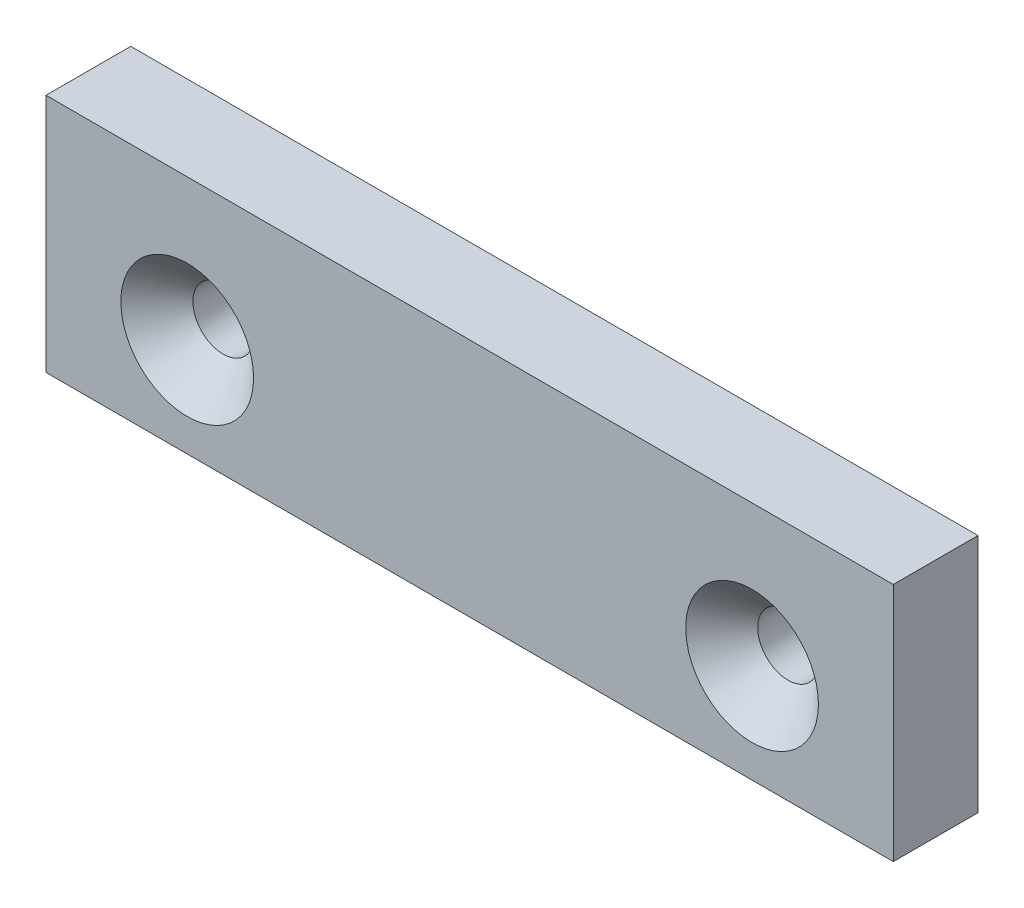
SolidWorks part; units mm, degrees
ref_plane "Płaszczyzna przednia" through (0, 0, 0) normal (0, 0, 1) x (1, 0, 0)
ref_plane "Płaszczyzna górna" through (0, 0, 0) normal (0, 1, 0) x (1, 0, 0)
ref_plane "Płaszczyzna prawa" through (0, 0, 0) normal (1, 0, 0) x (0, 0, -1)
sketch "Sketch1" plane through (0, 0, 0) normal (0, 0, 1) x (1, 0, 0)
  line L1 (0, 0) -> (60, 0)
  line L2 (0, 0) -> (0, 17)
  line L3 (0, 17) -> (60, 17)
  line L4 (60, 0) -> (60, 17)
  line L5 (0, 0) -> (60, 17) construction
  line L6 (0, 17) -> (60, 0) construction
  point P4 (30, 8.5)
  dimension "D1" = 17
  dimension "60" = 60
extrude "Boss-Extrude1" add sketch "Sketch1" along normal blind 6
hole_wizard "CSK for M4 Flat Head Machine Screw1" positions "Sketch2" profile "Sketch3" countersink size "M4" standard "ANSI Metric" end condition up to next
sketch "Sketch2" plane through (0, 0, 6) normal (0, 0, 1) x (1, 0, 0)
  line L0 (0, 17) -> (0, 0) construction
  line L1 (60, 0) -> (60, 17) construction
  line L2 (60, 17) -> (0, 17) construction
  point P0 (10, 7)
  point P2 (50, 7)
  dimension "D1" = 10
  dimension "D2" = 10
  dimension "D3" = 10
  dimension "D4" = 10
sketch "Sketch3" plane through (10, 7, 6) normal (1, 0, 0) x (0, -1, 0)
  line L0 (0, 0) -> (0, 6)
  line L1 (0, 6) -> (2.15, 6)
  line L2 (2.15, 6) -> (2.15, 2.55)
  line L3 (2.15, 2.55) -> (4.7, 0)
  line L5 (4.7, 0) -> (0, 0)
  line L6 (-2.15, 2.55) -> (-4.7, 0) construction
  line L11 (0, -6.35) -> (0, 107.95) construction
  dimension "Thru Hole Dia." = 4.3
  dimension "Thru Hole Depth" = 6
  dimension "Near C'Sink Dia." = 9.4
  dimension "Near C'Sink Angle" = 90
